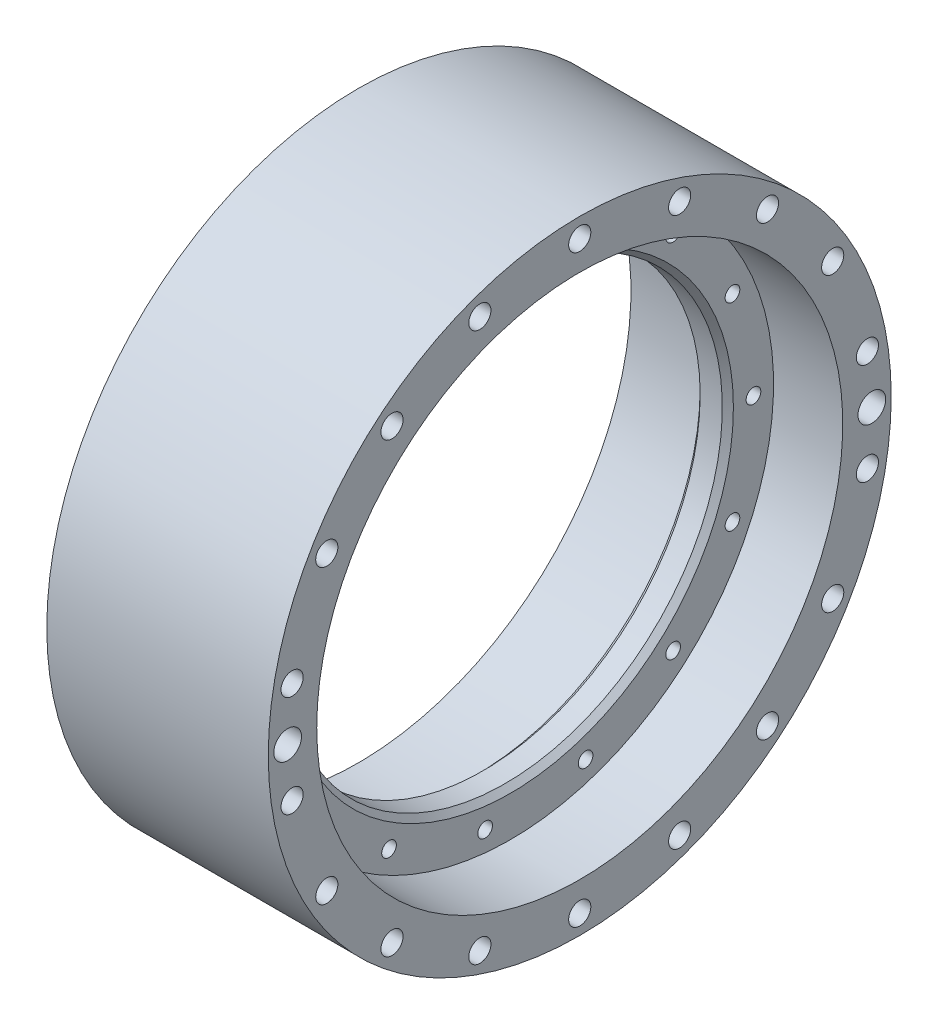
SolidWorks part; units mm, degrees
ref_plane "Front Plane" through (0, 0, 0) normal (0, 0, 1) x (1, 0, 0)
ref_plane "Top Plane" through (0, 0, 0) normal (0, 1, 0) x (1, 0, 0)
ref_plane "Right Plane" through (0, 0, 0) normal (1, 0, 0) x (0, 0, -1)
sketch "Sketch1" plane through (0, 0, 0) normal (0, 0, 1) x (1, 0, 0)
  line L0 (0, 112.5) -> (80, 112.5)
  line L1 (80, 112.5) -> (80, 95)
  line L3 (55, 95) -> (55, 78.5)
  line L4 (55, 78.5) -> (43, 78.5)
  line L5 (43, 78.5) -> (43, 98.5)
  line L6 (43, 98.5) -> (0, 98.5)
  line L7 (0, 98.5) -> (0, 112.5)
  line L8 (0, 0) -> (89.4597, 0) construction
  line L9 (27.6099, 87.75) -> (95.1089, 87.75) construction
  line L10 (55, 95) -> (80, 95)
  dimension "D1" = 98.5
  dimension "D2" = 112.5
  dimension "D3" = 25
  dimension "D4" = 12
  dimension "D5" = 20
  dimension "D6" = 80
  dimension "D7" = 87.75
  dimension "D8" = 95
revolve "Revolve1" add sketch "Sketch1" angle 360 about L8
sketch "Sketch2" plane through (0, 0, 0) normal (-1, 0, 0) x (0, 0, 1)
  line L0 (0, 112.5) -> (0, 98.5) construction
  circle A1 centre (0, 0) radius 112.5 construction
  circle A2 centre (0, 0) radius 98.5 construction
  point P0 (0, 105.5)
hole_wizard "Ø8.0mm Dowel Hole1" positions "3DSketch1" profile "Sketch3" hole size "Ø8.0" standard "ISO" end condition through all
sketch3d "3DSketch1"
  point P0 (0, 105.5, 0)
sketch "Sketch3" plane through (0, 105.5, 0) normal (0, 1, 0) x (0, 0, 1)
  line L0 (0, 0) -> (0, 80)
  line L1 (0, 80) -> (4, 80)
  line L2 (4, 80) -> (4, 0)
  line L5 (4, 0) -> (0, 0)
  line L11 (0, -6.35) -> (0, 107.95) construction
  dimension "Thru Hole Dia." = 8
  dimension "Thru Hole Depth" = 80
ref_axis "Axis1" through (80, 0, 0) along (-1, 0, 0)
pattern_circular "CirPattern1" count 18 over 360 about axis through (80, 0, 0) along (-1, 0, 0) of "Ø8.0mm Dowel Hole1"
sketch "Sketch4" plane through (0, 0, 0) normal (-1, 0, 0) x (0, 0, 1)
  line L0 (112.5, 0) -> (98.5, 0) construction
  line L1 (0, 0) -> (0, 33.1049) construction
  circle A0 centre (0, 0) radius 112.5 construction
  circle A1 centre (0, 0) radius 98.5 construction
  circle A2 centre (105.5, 0) radius 5
  circle A3 centre (-105.5, 0) radius 5
  dimension "D1" = 10
extrude "Cut-Extrude1" cut sketch "Sketch4" against normal through all
sketch "Sketch5" plane through (55, 0, 0) normal (1, 0, 0) x (0, 0, -1)
  circle A0 centre (87.75, 0) radius 2.65
  circle A3 centre (0, 0) radius 87.75 construction
  dimension "D1" = 5.3
  dimension "D2" = 175.5
extrude "Cut-Extrude2" cut sketch "Sketch5" against normal through all
pattern_circular "CirPattern2" count 15 over 360 about axis through (80, 0, 0) along (-1, 0, 0) of "Cut-Extrude2"
chamfer "Chamfer1" distance 2 angle 45 2 edges at (43, 0, 78.5) (55, 0, 78.5)
